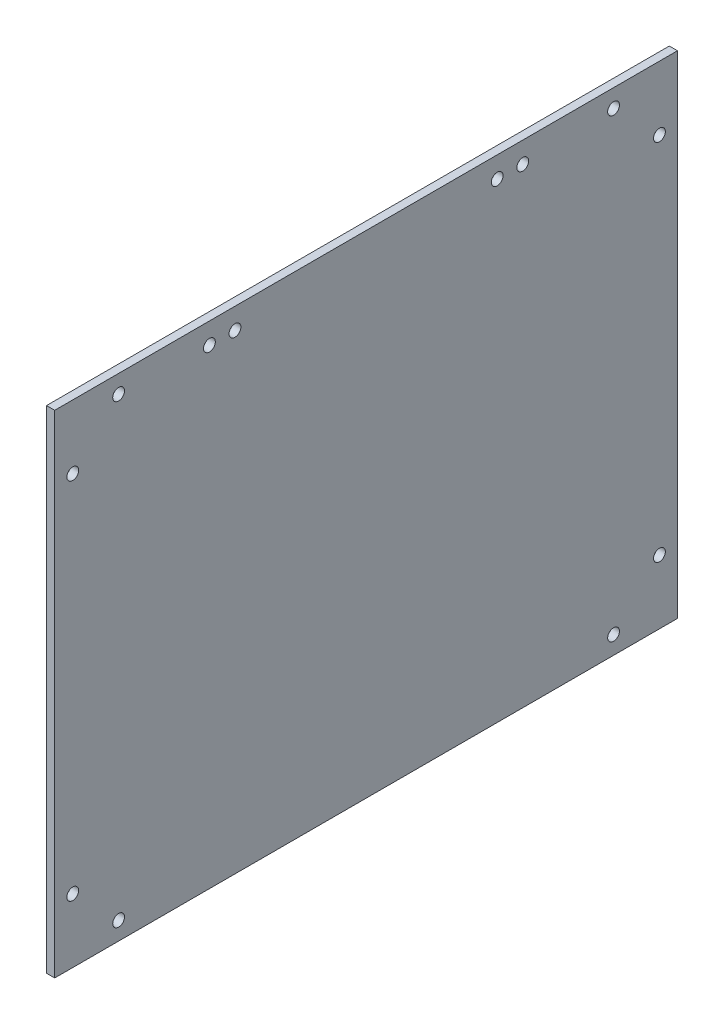
SolidWorks part; units mm, degrees
ref_plane "Front Plane" through (0, 0, 0) normal (0, 0, 1) x (1, 0, 0)
ref_plane "Top Plane" through (0, 0, 0) normal (0, 1, 0) x (1, 0, 0)
ref_plane "Right Plane" through (0, 0, 0) normal (1, 0, 0) x (0, 0, -1)
sketch "Sketch1" plane through (0, 0, 0) normal (1, 0, 0) x (0, 0, -1)
  line L1 (0, 0) -> (241.3, 0)
  line L2 (0, 0) -> (0, 190.5)
  line L3 (0, 190.5) -> (241.3, 190.5)
  line L4 (241.3, 0) -> (241.3, 190.5)
  dimension "D1" = 241.3
  dimension "D2" = 190.5
extrude "Boss-Extrude1" add sketch "Sketch1" along normal blind 3.175
sketch "Sketch2" plane through (3.175, 0, 0) normal (1, 0, 0) x (0, 0, -1)
  line L0 (241.3, 0) -> (241.3, 190.5) construction
  line L1 (0, 0) -> (241.3, 0) construction
  line L2 (-1000, 95.25) -> (49000, 95.25) construction
  line L3 (0, 190.5) -> (0, 0) construction
  line L4 (120.65, -809.5) -> (120.65, 49190.5) construction
  line L5 (241.3, 190.5) -> (0, 190.5) construction
  line L6 (1228.6, 95.25) -> (-48771.4, 95.25) construction
  circle A0 centre (216.535, 6.985) radius 2.286
  circle A1 centre (234.315, 24.765) radius 2.286
  circle A2 centre (234.315, 165.735) radius 2.286
  circle A3 centre (216.535, 183.515) radius 2.286
  circle A4 centre (24.765, 183.515) radius 2.286
  circle A5 centre (6.985, 165.735) radius 2.286
  circle A6 centre (6.985, 24.765) radius 2.286
  circle A7 centre (24.765, 6.985) radius 2.286
  point P15 (0, 95.25)
  point P20 (120.65, 190.5)
  dimension "D1" = 4.572
  dimension "D2" = 6.985
  dimension "D3" = 24.765
  dimension "D4" = 6.985
  dimension "D5" = 24.765
extrude "Cut-Extrude1" cut sketch "Sketch2" against normal through all
sketch "Sketch3" plane through (3.175, 0, 0) normal (1, 0, 0) x (0, 0, -1)
  line L0 (62.23, 182.372) -> (67.564, 182.372) construction
  line L1 (173.736, 182.372) -> (179.07, 182.372) construction
  line L2 (241.3, 190.5) -> (0, 190.5) construction
  circle A0 centre (59.944, 182.372) radius 2.286
  circle A1 centre (69.85, 182.372) radius 2.286
  circle A2 centre (171.45, 182.372) radius 2.286
  circle A3 centre (181.356, 182.372) radius 2.286
  point P14 (120.65, 190.5)
  point P15 (0, 0)
  point P16 (0, 0)
  dimension "D2" = 4.572
  dimension "D1" = 5.334
  dimension "D3" = 5.334
  dimension "D4" = 8.128
  dimension "D5" = 50.8
  dimension "D6" = 50.8
extrude "Cut-Extrude2" cut sketch "Sketch3" against normal through all
